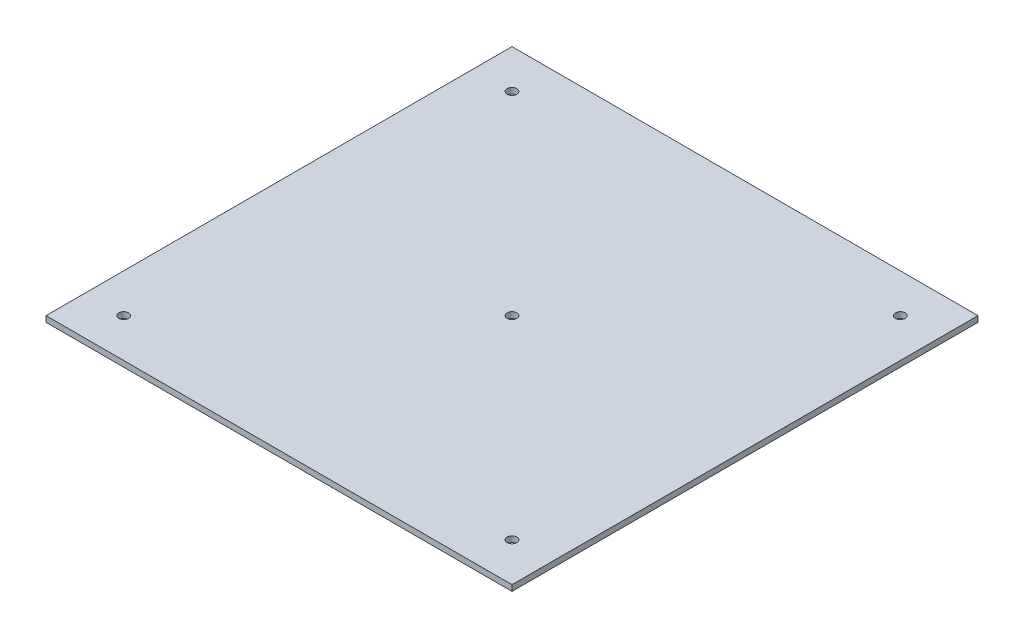
SolidWorks part; units mm, degrees
ref_plane "前视基准面" through (0, 0, 0) normal (0, 0, 1) x (1, 0, 0)
ref_plane "上视基准面" through (0, 0, 0) normal (0, 1, 0) x (1, 0, 0)
ref_plane "右视基准面" through (0, 0, 0) normal (1, 0, 0) x (0, 0, -1)
sketch "草图1" plane through (0, 0, 0) normal (0, 1, 0) x (1, 0, 0)
  line L0 (0, 120) -> (452.0299, 120) construction
  line L1 (0, 0) -> (240, 0)
  line L2 (0, 0) -> (0, 240)
  line L3 (0, 240) -> (240, 240)
  line L4 (240, 0) -> (240, 240)
  line L5 (120, 240) -> (120, -208.1919) construction
  line L6 (120, 120) -> (0, 240) construction
  circle A0 centre (120, 120) radius 2.5
  circle A1 centre (20, 220) radius 2.5
  circle A2 centre (220, 220) radius 2.5
  circle A3 centre (220, 20) radius 2.5
  circle A4 centre (20, 20) radius 2.5
  point P22 (120, 120)
  dimension "D3" = 5
  dimension "D4" = 5
  dimension "D5" = 20
  dimension "D1" = 240
  dimension "D2" = 240
  dimension "D6" = 4
extrude "凸台-拉伸1" add sketch "草图1" along normal blind 3
